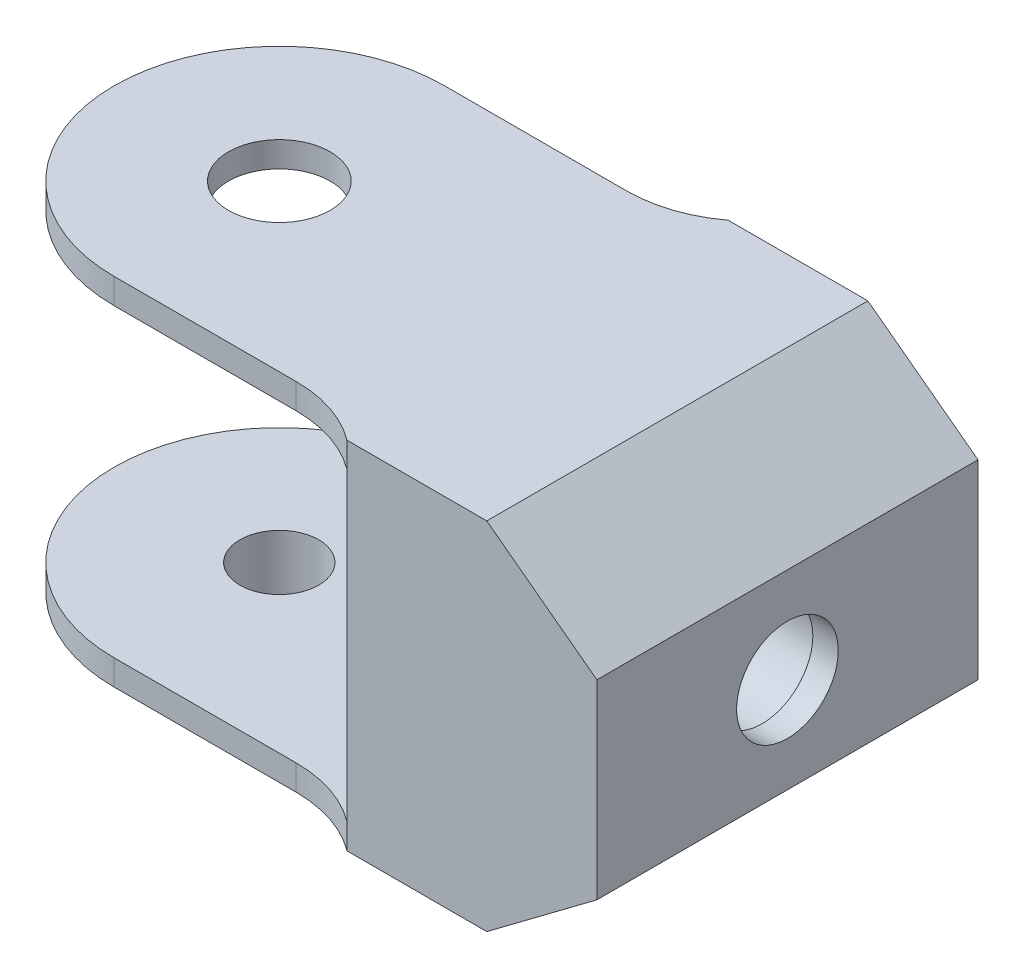
SolidWorks part; units mm, degrees
ref_plane "Front Plane" through (0, 0, 0) normal (0, 0, 1) x (1, 0, 0)
ref_plane "Top Plane" through (0, 0, 0) normal (0, 1, 0) x (1, 0, 0)
ref_plane "Right Plane" through (0, 0, 0) normal (1, 0, 0) x (0, 0, -1)
sketch "Sketch1" plane through (0, 0, 0) normal (0, 1, 0) x (1, 0, 0)
  line L1 (40, 13) -> (0, 13)
  line L2 (40, 13) -> (40, -13)
  line L3 (40, -13) -> (0, -13)
  arc A0 (0, 13) -> (0, -13) centre (0, 0) ccw
  dimension "D1" = 26
  dimension "D2" = 40
extrude "Boss-Extrude1" add sketch "Sketch1" along normal blind 2
sketch "Sketch2" plane through (0, 2, 0) normal (0, 1, 0) x (1, 0, 0)
  line L0 (0, -13) -> (40, -13) construction
  line L1 (40, 13) -> (38, 13)
  line L2 (40, 13) -> (40, -13)
  line L3 (40, -13) -> (38, -13)
  line L4 (38, 13) -> (38, -13)
  dimension "D1" = 2
extrude "Boss-Extrude2" add sketch "Sketch2" along normal blind 24
sketch "Sketch3" plane through (0, 26, 0) normal (0, 1, 0) x (1, 0, 0)
  line L1 (40, -13) -> (0, -13)
  line L2 (40, -13) -> (40, 13)
  line L3 (40, 13) -> (0, 13)
  arc A0 (0, 13) -> (0, -13) centre (0, 0) ccw
extrude "Boss-Extrude3" add sketch "Sketch3" along normal blind 2
sketch "Sketch4" plane through (40, 0, 0) normal (1, 0, 0) x (0, 0, -1)
  line L0 (-13, 28) -> (13, 28) construction
  line L1 (-13, 28) -> (-13, 0) construction
  circle A0 centre (0, 14) radius 4
  point P5 (0, 28)
  point P8 (-13, 14)
  dimension "D1" = 8
extrude "Cut-Extrude1" cut sketch "Sketch4" against normal blind 2
sketch "Sketch5" plane through (0, 0, 13) normal (0, 0, 1) x (1, 0, 0)
  line L0 (38, 5) -> (34, 2)
  line L9 (34, 2) -> (31.3333, 0)
  line L10 (0, 0) -> (40, 0) construction
  line L11 (31.3333, 0) -> (31.3333, 2)
  line L12 (0, 2) -> (38, 2) construction
  line L13 (31.3333, 2) -> (40, 8.5)
  line L14 (40, 28) -> (40, 0) construction
  line L15 (40, 8.5) -> (40, 6.5)
  line L16 (40, 6.5) -> (38, 5)
  line L17 (40, 14) -> (19.1052, 14) construction
  line L18 (40, 21.5) -> (38, 23)
  line L19 (40, 19.5) -> (40, 21.5)
  line L20 (31.3333, 26) -> (40, 19.5)
  line L21 (31.3333, 28) -> (31.3333, 26)
  line L22 (34, 26) -> (31.3333, 28)
  line L23 (38, 23) -> (34, 26)
  dimension "D5" = 2
extrude "Boss-Extrude4" add sketch "Sketch5" against normal up to surface (26 mm away) up to face at (19.5, 14, -13)
sketch "Sketch6" plane through (0, 0, 13) normal (0, 0, 1) x (1, 0, 0)
  line L0 (38, 5) -> (31.3333, 0)
  line L1 (0, 0) -> (40, 0) construction
  line L2 (31.3333, 0) -> (40, 0)
  line L3 (40, 0) -> (40, 6.5)
  line L4 (40, 28) -> (40, 0) construction
  line L5 (40, 6.5) -> (38, 5)
  line L6 (34, 2) -> (38, 5) construction
  line L7 (40, 14) -> (25.7632, 14) construction
  line L8 (40, 28) -> (40, 21.5)
  line L9 (31.3333, 28) -> (40, 28)
  line L10 (38, 23) -> (31.3333, 28)
  line L11 (40, 21.5) -> (38, 23)
extrude "Cut-Extrude2" cut sketch "Sketch6" against normal up to surface (26 mm away) up to face at (36.6667, 3, -13)
sketch "Sketch7" plane through (0, 0, 13) normal (0, 0, 1) x (1, 0, 0)
  line L0 (40, 21.5) -> (31.3333, 28)
  line L1 (31.3333, 28) -> (20.3333, 28)
  line L2 (0, 28) -> (31.3333, 28) construction
  line L3 (20.3333, 28) -> (20.3333, 0)
  line L4 (0, 0) -> (31.3333, 0) construction
  line L5 (20.3333, 0) -> (31.3333, 0)
  line L6 (31.3333, 0) -> (40, 6.5)
  line L7 (40, 6.5) -> (40, 21.5)
  dimension "D1" = 11
extrude "Boss-Extrude5" add sketch "Sketch7" along normal blind 2
ref_plane "Plane1" through (0, 0, 0) normal (0, 0, 1) x (1, 0, 0)
mirror "Mirror1" about plane through (0, 0, 0) normal (0, 0, 1) of "Boss-Extrude5"
sketch "Sketch8" plane through (38, 0, 0) normal (-1, 0, 0) x (0, 0, 1)
  circle A0 centre (0, 14) radius 4.4884
  circle A1 centre (0, 14) radius 7.515
extrude "Boss-Extrude6" add sketch "Sketch8" along normal blind 4
sketch "Sketch9" plane through (0, 0, 0) normal (0, -1, 0) x (1, 0, 0)
  circle A0 centre (0, 0) radius 3.1
  dimension "D1" = 6.2
extrude "Cut-Extrude3" cut sketch "Sketch9" against normal blind 10
sketch "Sketch10" plane through (0, 28, 0) normal (0, 1, 0) x (1, 0, 0)
  circle A0 centre (0, 0) radius 4
  dimension "D1" = 8
extrude "Cut-Extrude4" cut sketch "Sketch10" against normal blind 10
sketch "Sketch11" plane through (0, 0, 0) normal (0, -1, 0) x (1, 0, 0)
  circle A0 centre (0, 0) radius 3.1
  circle A1 centre (0, 0) radius 4
  dimension "D1" = 8
  dimension "D2" = 6.2
extrude "Boss-Extrude7" add sketch "Sketch11" along normal blind 7
sketch "Sketch12" plane through (0, -7, 0) normal (0, -1, 0) x (1, 0, 0)
  circle A0 centre (0, 0) radius 4
extrude "Boss-Extrude8" add sketch "Sketch12" along normal blind 1
sketch "Sketch13" plane through (0, 0, 15) normal (0, 0, 1) x (1, 0, 0)
  line L0 (20.3333, 28) -> (20.3333, 0) construction
  line L1 (25.3333, 19) -> (30.3333, 19)
  line L2 (25.3333, 19) -> (25.3333, 9)
  line L3 (25.3333, 9) -> (30.3333, 9)
  line L4 (30.3333, 19) -> (30.3333, 9)
  line L5 (40, 6.5) -> (40, 21.5) construction
  point P8 (40, 14)
  point P9 (30.3333, 14)
  dimension "D1" = 10
  dimension "D2" = 5
  dimension "D3" = 5
extrude "Cut-Extrude5" cut sketch "Sketch13" against normal blind 10
sketch "Sketch14" plane through (0, 0, -15) normal (0, 0, -1) x (-1, 0, 0)
  line L1 (-30.3333, 19) -> (-25.3333, 19)
  line L2 (-30.3333, 19) -> (-30.3333, 9)
  line L3 (-30.3333, 9) -> (-25.3333, 9)
  line L4 (-25.3333, 19) -> (-25.3333, 9)
extrude "Cut-Extrude6" cut sketch "Sketch14" against normal blind 4
sketch "Sketch15" plane through (0, 0, 15) normal (0, 0, 1) x (1, 0, 0)
  line L1 (25.3333, 19) -> (30.3333, 19)
  line L2 (25.3333, 19) -> (25.3333, 9)
  line L3 (25.3333, 9) -> (30.3333, 9)
  line L4 (30.3333, 19) -> (30.3333, 9)
extrude "Boss-Extrude9" add sketch "Sketch15" against normal blind 2
sketch "Sketch16" plane through (0, 0, -15) normal (0, 0, -1) x (-1, 0, 0)
  line L1 (-25.3333, 19) -> (-30.3333, 19)
  line L2 (-25.3333, 19) -> (-25.3333, 21)
  line L3 (-25.3333, 21) -> (-30.3333, 21)
  line L4 (-30.3333, 19) -> (-30.3333, 21)
  line L5 (-30.3333, 9) -> (-25.3333, 9)
  line L6 (-30.3333, 9) -> (-30.3333, 7)
  line L7 (-30.3333, 7) -> (-25.3333, 7)
  line L8 (-25.3333, 9) -> (-25.3333, 7)
  dimension "D1" = 2
  dimension "2" = 2
extrude "Boss-Extrude10" add sketch "Sketch16" along normal blind 2
sketch "Sketch17" plane through (0, 0, -17) normal (0, 0, -1) x (-1, 0, 0)
  line L1 (-30.3333, 21) -> (-25.3333, 21)
  line L2 (-30.3333, 21) -> (-30.3333, 7)
  line L3 (-30.3333, 7) -> (-25.3333, 7)
  line L4 (-25.3333, 21) -> (-25.3333, 7)
extrude "Boss-Extrude11" add sketch "Sketch17" along normal blind 2
fillet "Fillet1" radius 10 4 edges at (20.3333, 1, -13) (20.3333, 27, -13) (20.3333, 27, 13) (20.3333, 1, 13)
